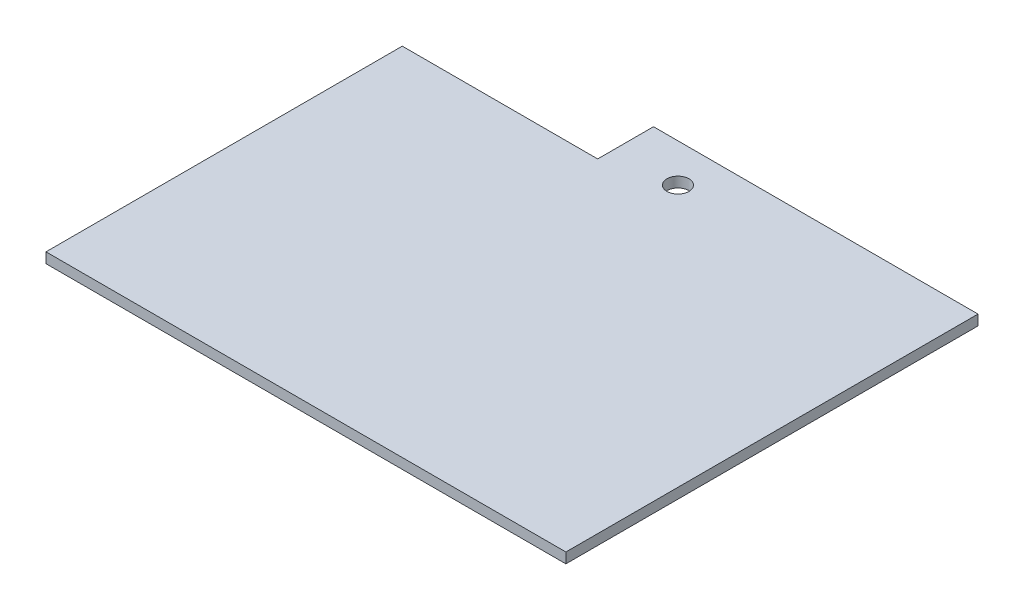
SolidWorks part; units mm, degrees
ref_plane "Front Plane" through (0, 0, 0) normal (0, 0, 1) x (1, 0, 0)
ref_plane "Top Plane" through (0, 0, 0) normal (0, 1, 0) x (1, 0, 0)
ref_plane "Right Plane" through (0, 0, 0) normal (1, 0, 0) x (0, 0, -1)
sketch "Sketch1" plane through (0, 0, 0) normal (0, 1, 0) x (1, 0, 0)
  line L0 (37.845, 30) -> (-0.255, 30)
  line L1 (-37.845, 30) -> (37.845, 30)
  line L2 (-37.845, 30) -> (-37.845, -30)
  line L3 (-37.845, -30) -> (37.845, -30)
  line L4 (37.845, 30) -> (37.845, -30)
  line L5 (-37.845, 30) -> (37.845, -30) construction
  line L6 (-37.845, -30) -> (37.845, 30) construction
  line L7 (-0.255, 30) -> (-0.255, 24.42) construction
  line L8 (-8.7319, 30) -> (-8.7319, 21.872)
  line L9 (-37.845, 30) -> (-37.845, 21.872)
  line L10 (-37.845, 21.872) -> (-9.397, 21.872)
  line L12 (-37.845, 30) -> (-9.397, 30)
  line L13 (-37.845, 30) -> (-37.845, 21.872)
  line L14 (-37.845, 21.872) -> (-9.397, 21.872)
  line L15 (-9.397, 30) -> (-9.397, 21.872)
  circle A0 centre (-0.255, 24.42) radius 1.6
  point P0 (0, 0)
  dimension "D5" = 3.2
  dimension "D1" = 75.69
  dimension "D2" = 60
  dimension "D3" = 38.1
  dimension "D4" = 5.58
  dimension "D6" = 8.128
  dimension "D7" = 28.448
extrude "Boss-Extrude1" add sketch "Sketch1" along normal blind 1.5 contours L4 L0 L1 L2 L3 A0 region at (1.27, 0, 1.4396)
